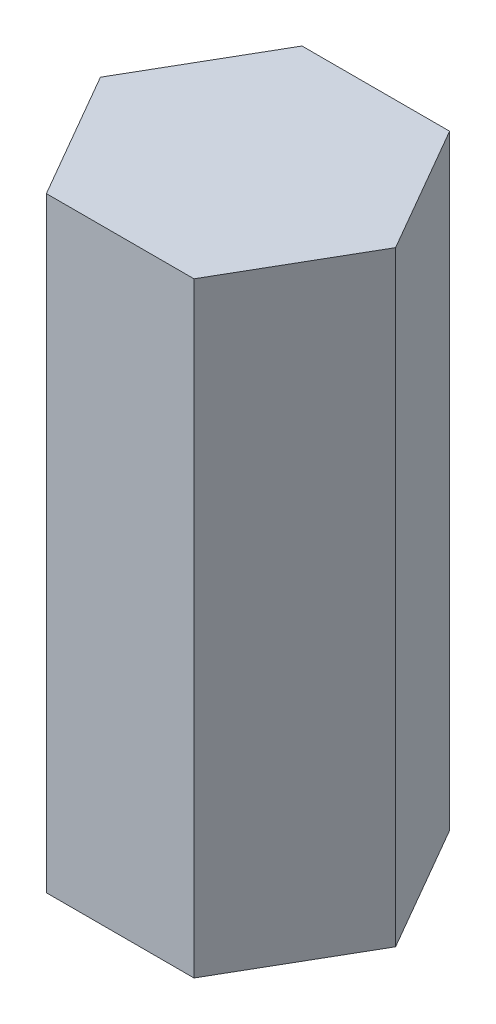
SolidWorks part; units mm, degrees
ref_plane "Front Plane" through (0, 0, 0) normal (0, 0, 1) x (1, 0, 0)
ref_plane "Top Plane" through (0, 0, 0) normal (0, 1, 0) x (1, 0, 0)
ref_plane "Right Plane" through (0, 0, 0) normal (1, 0, 0) x (0, 0, -1)
sketch "Sketch1" plane through (0, 0, 0) normal (0, 1, 0) x (1, 0, 0)
  line L1 (19.5, 0) -> (9.75, 16.8875)
  line L2 (9.75, 16.8875) -> (-9.75, 16.8875)
  line L3 (-9.75, 16.8875) -> (-19.5, 0)
  line L4 (-19.5, 0) -> (-9.75, -16.8875)
  line L5 (-9.75, -16.8875) -> (9.75, -16.8875)
  line L6 (9.75, -16.8875) -> (19.5, 0)
  circle A0 centre (0, 0) radius 16.8875 construction
  point P1 (-10.2668, -16.5784)
  point P10 (0, 0)
  dimension "D1" = 19.5
extrude "Boss-Extrude1" add sketch "Sketch1" along normal mid plane 80
ref_axis "Axis1" through (0, 44, 0) along (0, -1, 0)
